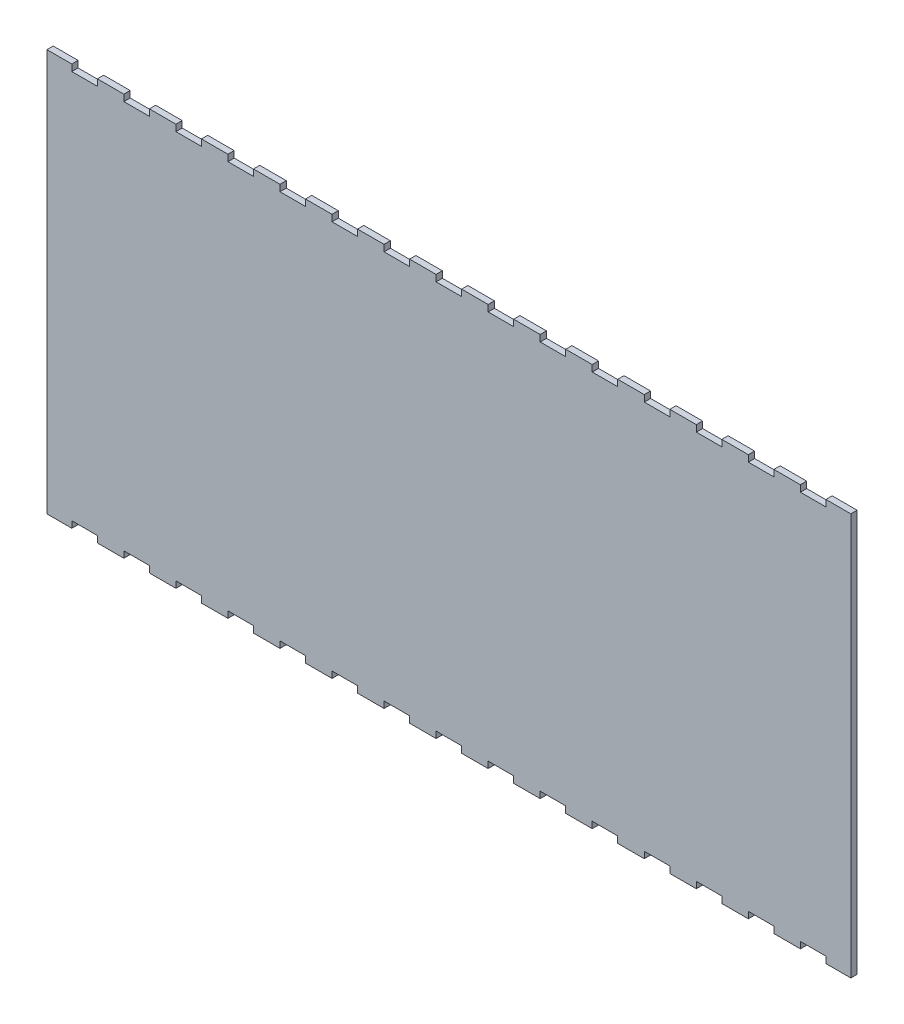
SolidWorks part; units mm, degrees
ref_plane "Front Plane" through (0, 0, 0) normal (0, 0, 1) x (1, 0, 0)
ref_plane "Top Plane" through (0, 0, 0) normal (0, 1, 0) x (1, 0, 0)
ref_plane "Right Plane" through (0, 0, 0) normal (1, 0, 0) x (0, 0, -1)
sketch "Sketch1" plane through (0, 0, 0) normal (0, 0, 1) x (1, 0, 0)
  line L248 (393.8, 203.2) -> (393.8, 199.925)
  line L249 (393.8, 199.925) -> (380.9, 199.925)
  line L250 (380.9, 199.925) -> (380.9, 203.2)
  line L251 (380.9, 203.2) -> (367.4929, 203.2)
  line L252 (367.4929, 203.2) -> (367.4929, 199.925)
  line L253 (367.4929, 199.925) -> (354.5929, 199.925)
  line L254 (354.5929, 199.925) -> (354.5929, 203.2)
  line L255 (354.5929, 203.2) -> (341.1857, 203.2)
  line L256 (341.1857, 203.2) -> (341.1857, 199.925)
  line L257 (341.1857, 199.925) -> (328.2857, 199.925)
  line L258 (328.2857, 199.925) -> (328.2857, 203.2)
  line L259 (328.2857, 203.2) -> (314.8786, 203.2)
  line L260 (314.8786, 203.2) -> (314.8786, 199.925)
  line L261 (314.8786, 199.925) -> (301.9786, 199.925)
  line L262 (301.9786, 199.925) -> (301.9786, 203.2)
  line L263 (301.9786, 203.2) -> (288.5714, 203.2)
  line L264 (288.5714, 203.2) -> (288.5714, 199.925)
  line L265 (288.5714, 199.925) -> (275.6714, 199.925)
  line L266 (275.6714, 199.925) -> (275.6714, 203.2)
  line L267 (275.6714, 203.2) -> (262.2643, 203.2)
  line L268 (262.2643, 203.2) -> (262.2643, 199.925)
  line L269 (262.2643, 199.925) -> (249.3643, 199.925)
  line L270 (249.3643, 199.925) -> (249.3643, 203.2)
  line L271 (249.3643, 203.2) -> (235.9571, 203.2)
  line L272 (235.9571, 203.2) -> (235.9571, 199.925)
  line L273 (235.9571, 199.925) -> (223.0571, 199.925)
  line L274 (223.0571, 199.925) -> (223.0571, 203.2)
  line L275 (223.0571, 203.2) -> (209.65, 203.2)
  line L276 (209.65, 203.2) -> (209.65, 199.925)
  line L277 (209.65, 199.925) -> (196.75, 199.925)
  line L278 (196.75, 199.925) -> (196.75, 203.2)
  line L279 (196.75, 203.2) -> (183.3429, 203.2)
  line L280 (183.3429, 203.2) -> (183.3429, 199.925)
  line L281 (183.3429, 199.925) -> (170.4429, 199.925)
  line L282 (170.4429, 199.925) -> (170.4429, 203.2)
  line L283 (170.4429, 203.2) -> (157.0357, 203.2)
  line L284 (157.0357, 203.2) -> (157.0357, 199.925)
  line L285 (157.0357, 199.925) -> (144.1357, 199.925)
  line L286 (144.1357, 199.925) -> (144.1357, 203.2)
  line L287 (144.1357, 203.2) -> (130.7286, 203.2)
  line L288 (130.7286, 203.2) -> (130.7286, 199.925)
  line L289 (130.7286, 199.925) -> (117.8286, 199.925)
  line L290 (117.8286, 199.925) -> (117.8286, 203.2)
  line L291 (117.8286, 203.2) -> (104.4214, 203.2)
  line L292 (104.4214, 203.2) -> (104.4214, 199.925)
  line L293 (104.4214, 199.925) -> (91.5214, 199.925)
  line L294 (91.5214, 199.925) -> (91.5214, 203.2)
  line L295 (91.5214, 203.2) -> (78.1143, 203.2)
  line L296 (78.1143, 203.2) -> (78.1143, 199.925)
  line L297 (78.1143, 199.925) -> (65.2143, 199.925)
  line L298 (65.2143, 199.925) -> (65.2143, 203.2)
  line L299 (65.2143, 203.2) -> (51.8071, 203.2)
  line L300 (51.8071, 203.2) -> (51.8071, 199.925)
  line L301 (51.8071, 199.925) -> (38.9071, 199.925)
  line L302 (38.9071, 199.925) -> (38.9071, 203.2)
  line L303 (38.9071, 203.2) -> (25.5, 203.2)
  line L304 (25.5, 203.2) -> (25.5, 199.925)
  line L305 (25.5, 199.925) -> (12.6, 199.925)
  line L306 (12.6, 199.925) -> (12.6, 203.2254)
  line L307 (12.6, 203.2254) -> (0, 203.2254)
  line L308 (0, 203.2254) -> (0, -0.0254)
  line L309 (0, -0.0254) -> (12.6, -0.0254)
  line L310 (12.6, -0.0254) -> (12.6, 3.275)
  line L311 (12.6, 3.275) -> (25.5, 3.275)
  line L312 (25.5, 3.275) -> (25.5, 0)
  line L313 (25.5, 0) -> (38.9071, 0)
  line L314 (38.9071, 0) -> (38.9071, 3.275)
  line L315 (38.9071, 3.275) -> (51.8071, 3.275)
  line L316 (51.8071, 3.275) -> (51.8071, 0)
  line L317 (51.8071, 0) -> (65.2143, 0)
  line L318 (65.2143, 0) -> (65.2143, 3.275)
  line L319 (65.2143, 3.275) -> (78.1143, 3.275)
  line L320 (78.1143, 3.275) -> (78.1143, 0)
  line L321 (78.1143, 0) -> (91.5214, 0)
  line L322 (91.5214, 0) -> (91.5214, 3.275)
  line L323 (91.5214, 3.275) -> (104.4214, 3.275)
  line L324 (104.4214, 3.275) -> (104.4214, 0)
  line L325 (104.4214, 0) -> (117.8286, 0)
  line L326 (117.8286, 0) -> (117.8286, 3.275)
  line L327 (117.8286, 3.275) -> (130.7286, 3.275)
  line L328 (130.7286, 3.275) -> (130.7286, 0)
  line L329 (130.7286, 0) -> (144.1357, 0)
  line L330 (144.1357, 0) -> (144.1357, 3.275)
  line L331 (144.1357, 3.275) -> (157.0357, 3.275)
  line L332 (157.0357, 3.275) -> (157.0357, 0)
  line L333 (157.0357, 0) -> (170.4429, 0)
  line L334 (170.4429, 0) -> (170.4429, 3.275)
  line L335 (170.4429, 3.275) -> (183.3429, 3.275)
  line L336 (183.3429, 3.275) -> (183.3429, 0)
  line L337 (183.3429, 0) -> (196.75, 0)
  line L338 (196.75, 0) -> (196.75, 3.275)
  line L339 (196.75, 3.275) -> (209.65, 3.275)
  line L340 (209.65, 3.275) -> (209.65, 0)
  line L341 (209.65, 0) -> (223.0571, 0)
  line L342 (223.0571, 0) -> (223.0571, 3.275)
  line L343 (223.0571, 3.275) -> (235.9571, 3.275)
  line L344 (235.9571, 3.275) -> (235.9571, 0)
  line L345 (235.9571, 0) -> (249.3643, 0)
  line L346 (249.3643, 0) -> (249.3643, 3.275)
  line L347 (249.3643, 3.275) -> (262.2643, 3.275)
  line L348 (262.2643, 3.275) -> (262.2643, 0)
  line L349 (262.2643, 0) -> (275.6714, 0)
  line L350 (275.6714, 0) -> (275.6714, 3.275)
  line L351 (275.6714, 3.275) -> (288.5714, 3.275)
  line L352 (288.5714, 3.275) -> (288.5714, 0)
  line L353 (288.5714, 0) -> (301.9786, 0)
  line L354 (301.9786, 0) -> (301.9786, 3.275)
  line L355 (301.9786, 3.275) -> (314.8786, 3.275)
  line L356 (314.8786, 3.275) -> (314.8786, 0)
  line L357 (314.8786, 0) -> (328.2857, 0)
  line L358 (328.2857, 0) -> (328.2857, 3.275)
  line L359 (328.2857, 3.275) -> (341.1857, 3.275)
  line L360 (341.1857, 3.275) -> (341.1857, 0)
  line L361 (341.1857, 0) -> (354.5929, 0)
  line L362 (354.5929, 0) -> (354.5929, 3.275)
  line L363 (354.5929, 3.275) -> (367.4929, 3.275)
  line L364 (367.4929, 3.275) -> (367.4929, 0)
  line L365 (367.4929, 0) -> (380.9, 0)
  line L366 (380.9, 0) -> (380.9, 3.275)
  line L367 (380.9, 3.275) -> (393.8, 3.275)
  line L368 (393.8, 3.275) -> (393.8, 0)
  line L369 (393.8, 0) -> (406.4, 0)
  line L370 (406.4, 0) -> (406.4, 203.2)
  line L371 (406.4, 203.2) -> (393.8, 203.2)
extrude "Boss-Extrude1" add sketch "Sketch1" along normal blind 3.175
